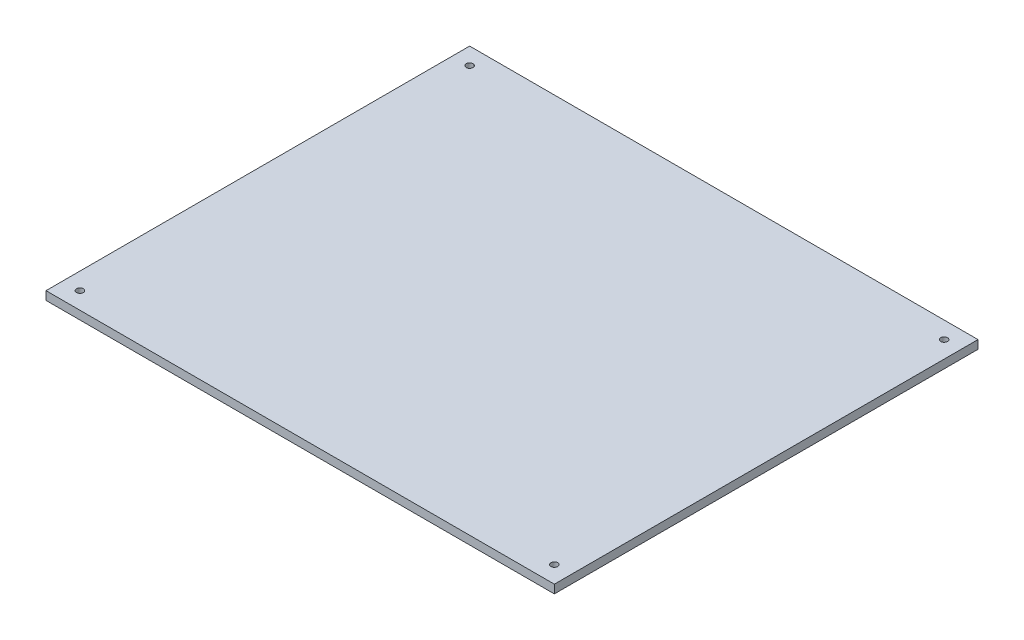
SolidWorks part; units mm, degrees
ref_plane "前视基准面" through (0, 0, 0) normal (0, 0, 1) x (1, 0, 0)
ref_plane "上视基准面" through (0, 0, 0) normal (0, 1, 0) x (1, 0, 0)
ref_plane "右视基准面" through (0, 0, 0) normal (1, 0, 0) x (0, 0, -1)
sketch "Sketch1" plane through (0, 0, 0) normal (0, 1, 0) x (1, 0, 0)
  line L0 (-140, -125) -> (-140, 125) construction
  line L1 (-150, -125) -> (150, -125)
  line L2 (-150, -125) -> (-150, 125)
  line L3 (-150, 125) -> (150, 125)
  line L4 (150, -125) -> (150, 125)
  line L5 (-150, -125) -> (150, 125) construction
  line L6 (-150, 125) -> (150, -125) construction
  line L7 (0, 0) -> (0, 125) construction
  line L8 (0, 0) -> (-150, 0) construction
  circle A0 centre (-140, -115) radius 2
  circle A1 centre (-140, 115) radius 2
  circle A2 centre (140, -115) radius 2
  circle A3 centre (140, 115) radius 2
  point P0 (0, 0)
  dimension "D4" = 4
  dimension "D5" = 10
  dimension "D1" = 300
  dimension "D2" = 250
  dimension "D3" = 10
extrude "Boss-Extrude1" add sketch "Sketch1" along normal blind 5
